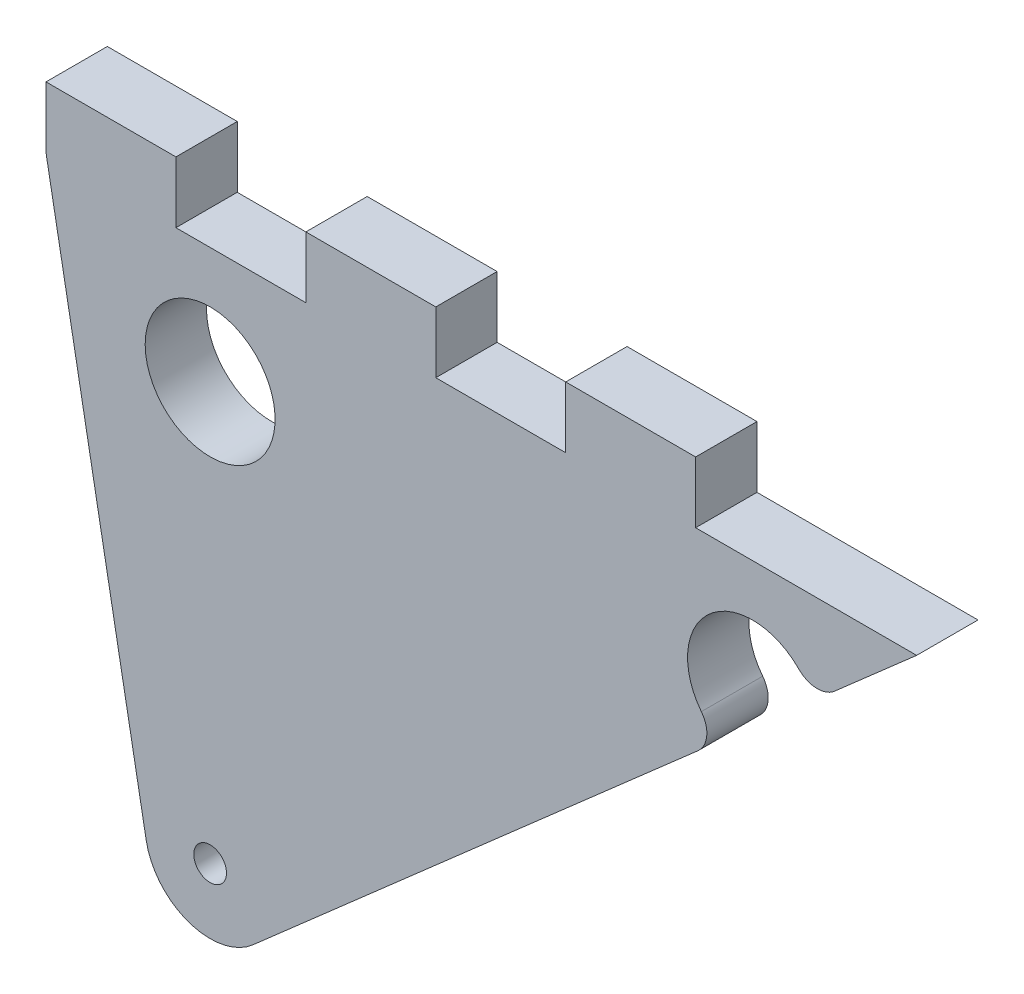
SolidWorks part; units mm, degrees
ref_plane "Front Plane" through (0, 0, 0) normal (0, 0, 1) x (1, 0, 0)
ref_plane "Top Plane" through (0, 0, 0) normal (0, 1, 0) x (1, 0, 0)
ref_plane "Right Plane" through (0, 0, 0) normal (1, 0, 0) x (0, 0, -1)
sketch "Sketch1" plane through (0, 0, 0) normal (0, 0, 1) x (1, 0, 0)
  line L1 (316.9956, 78.2168) -> (326.7498, 25.1342)
  line L2 (316.9538, 78.6758) -> (316.9538, 84.4388)
  line L3 (316.9538, 84.4388) -> (329.6538, 84.4388)
  line L5 (329.6538, 84.4388) -> (329.6538, 78.4444)
  line L7 (329.6538, 78.4444) -> (342.3538, 78.4444)
  line L9 (342.3538, 78.4444) -> (342.3538, 84.4388)
  line L10 (342.3538, 84.4388) -> (355.0538, 84.4388)
  line L11 (355.0538, 84.4388) -> (355.0538, 78.4444)
  line L12 (402.0588, 78.4444) -> (394.0278, 71.3959)
  line L13 (355.0538, 78.4444) -> (367.7538, 78.4444)
  line L14 (367.7538, 78.4444) -> (367.7538, 84.4388)
  line L15 (367.7538, 84.4388) -> (380.4538, 84.4388)
  line L16 (380.4538, 84.4388) -> (380.4538, 78.4444)
  line L18 (380.4538, 78.4444) -> (402.0588, 78.4444)
  line L19 (402.0588, 78.4444) -> (401.9903, 78.5437)
  line L20 (380.6863, 59.6866) -> (337.1864, 21.5084)
  circle A0 centre (332.9967, 26.2821) radius 1.6
  arc A1 (326.7498, 25.1342) -> (337.1864, 21.5084) centre (332.9967, 26.2821) ccw
  circle A2 centre (332.9967, 67.0694) radius 6.35
  arc A3 (390.5419, 71.5234) -> (381.0123, 63.1596) centre (386.0159, 67.0694) ccw
  arc A4 (316.9956, 78.2168) -> (316.9538, 78.6758) centre (319.4938, 78.6758) cw
  arc A5 (390.5419, 71.5234) -> (394.0278, 71.3959) centre (392.3523, 73.3049) ccw
  arc A6 (381.0123, 63.1596) -> (380.6863, 59.6866) centre (379.0108, 61.5957) cw
  point P35 (316.9538, 78.4444)
  point P41 (382.8357, 61.5731)
  dimension "D1" = 2.54
  dimension "D2" = 2.54
  dimension "D3" = 2.54
extrude "Boss-Extrude1" add sketch "Sketch1" along normal blind 5.9944 contours A6 A3 A5 L12 L18 L16 L15 L14 L13 L11 L10 L9 L7 L5 L3 L2 A4 L1 A1 L20 A2 A0 region at (349.011, 58.7083, 0)
